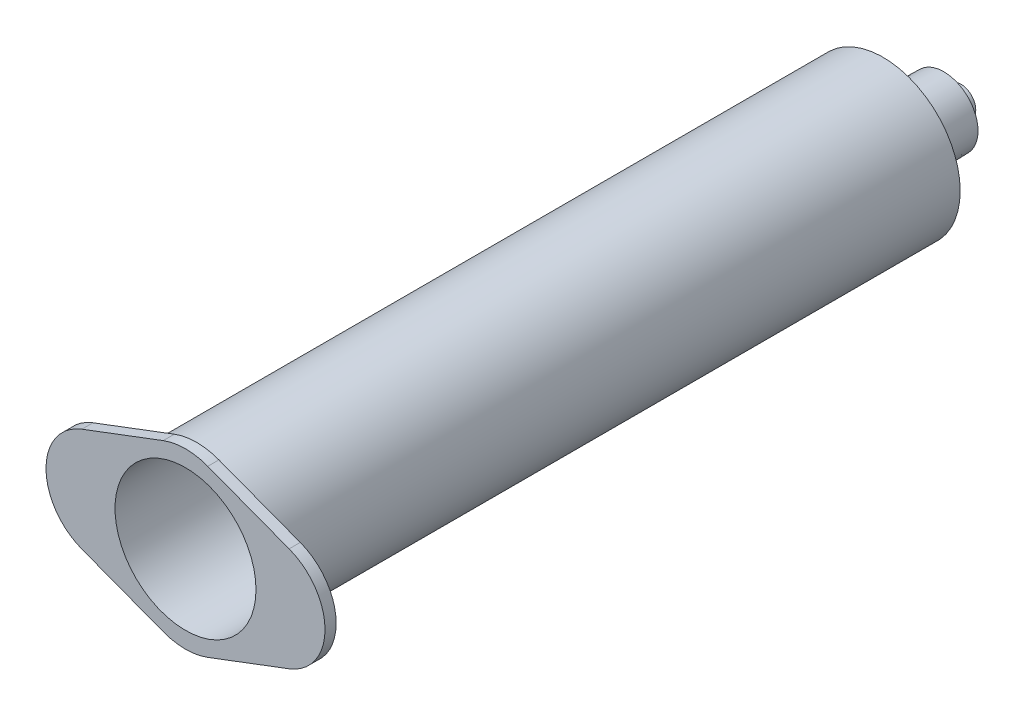
SolidWorks part; units mm, degrees
ref_plane "Front Plane" through (0, 0, 0) normal (0, 0, 1) x (1, 0, 0)
ref_plane "Top Plane" through (0, 0, 0) normal (0, 1, 0) x (1, 0, 0)
ref_plane "Right Plane" through (0, 0, 0) normal (1, 0, 0) x (0, 0, -1)
sketch "Sketch1" plane through (0, 0, 0) normal (0, 0, 1) x (1, 0, 0)
  circle A0 centre (0, 0) radius 9.5
  circle A1 centre (0, 0) radius 10.4
  dimension "D1" = 20.8
  dimension "D2" = 19
extrude "Boss-Extrude1" add sketch "Sketch1" along normal blind 92.5
sketch "Sketch2" plane through (0, 0, 0) normal (1, 0, 0) x (0, 0, -1)
  line L0 (0, 0) -> (12.896, 0) construction
  line L1 (0, 10.4) -> (1.2, 4.8)
  line L2 (1.2, 4.8) -> (8.2, 4.6)
  line L3 (8.2, 4.6) -> (8.2, 3.8)
  line L4 (8.2, 3.8) -> (2.2, 3.8)
  line L5 (2.2, 3.8) -> (2.2, 2)
  line L6 (2.2, 2) -> (10.5, 2)
  line L7 (10.5, 2) -> (10.5, 0.97)
  line L8 (10.5, 0.97) -> (1.2, 0.97)
  line L9 (1.2, 0.97) -> (1.2, 3.9)
  line L10 (1.2, 3.9) -> (0, 9.5)
  line L11 (0, 9.5) -> (0, 10.4)
  point P16 (10.0952, 3.321)
  point P17 (0, 0)
  point P18 (1.2, 1.2603)
  dimension "D1" = 1.94
  dimension "D2" = 4
  dimension "D3" = 9.2
  dimension "D4" = 9.6
  dimension "D5" = 7
  dimension "D6" = 2.3
  dimension "D7" = 1.2
  dimension "D8" = 6
  dimension "D9" = 0.8
revolve "Revolve1" add sketch "Sketch2" angle 360 about L0
sketch "Sketch3" plane through (0, 0, 92.5) normal (0, 0, 1) x (1, 0, 0)
  line L0 (0, 11.7) -> (0, 0) construction
  line L1 (0, 0) -> (-18.8, 0) construction
  line L2 (-3, 11.1511) -> (-13.9652, 7)
  line L3 (-3, -11.1511) -> (-13.9652, -7)
  line L4 (3, -11.1511) -> (13.9652, -7)
  line L5 (3, 11.1511) -> (13.9652, 7)
  circle A0 centre (0, 0) radius 9.5 construction
  circle A1 centre (0, 0) radius 9.5
  arc A2 (-13.9652, -7) -> (-13.9652, 7) centre (-11.3152, 0) cw
  arc A3 (3, 11.1511) -> (-3, 11.1511) centre (0, 3.2267) ccw
  arc A4 (3, -11.1511) -> (-3, -11.1511) centre (0, -3.2267) cw
  arc A5 (13.9652, -7) -> (13.9652, 7) centre (11.3152, 0) ccw
  point P9 (-9.5, 0)
  point P10 (0, 10.8094)
  point P11 (0, 9.5)
  point P12 (-15.5116, 0)
  point P13 (-8.8449, 9.6795)
  point P18 (-18.8, 0)
  point P19 (0, 0)
  point P24 (0, 11.7)
  dimension "D1" = 2.2
  dimension "D2" = 9.3
  dimension "D3" = 14
  dimension "D4" = 6
extrude "Boss-Extrude2" add sketch "Sketch3" along normal blind 1.5
